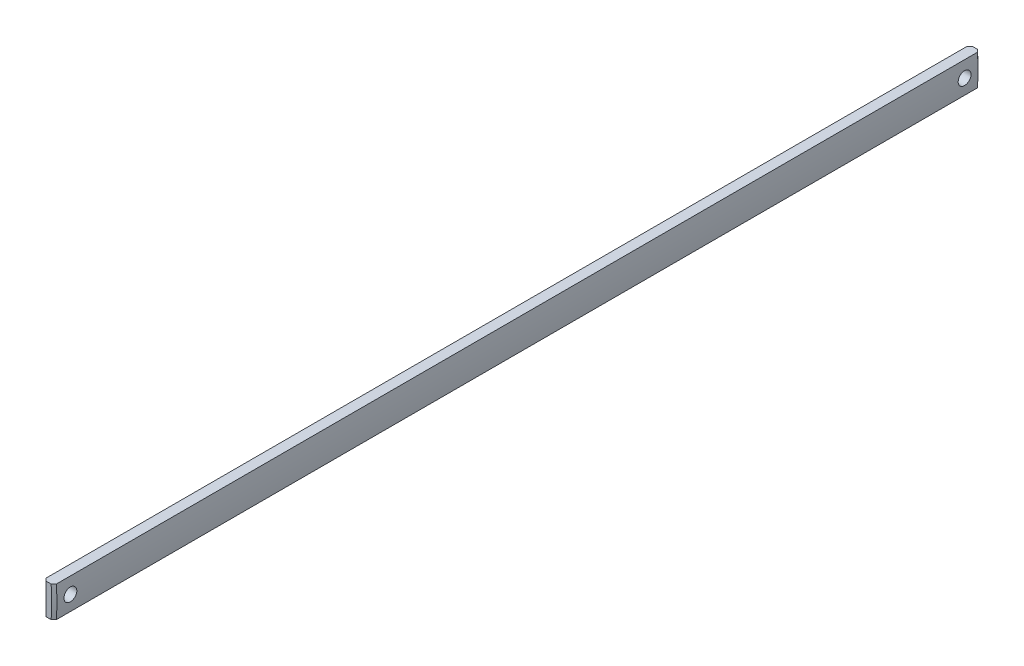
SolidWorks part; units mm, degrees
material "7075-T6, Piastra (SS)"
ref_plane "Piano frontale" through (0, 0, 0) normal (0, 0, 1) x (1, 0, 0)
ref_plane "Piano superiore" through (0, 0, 0) normal (0, 1, 0) x (1, 0, 0)
ref_plane "Piano destro" through (0, 0, 0) normal (1, 0, 0) x (0, 0, -1)
sketch "Schizzo1" plane through (0, 0, 0) normal (0, 0, 1) x (1, 0, 0)
  line L0 (68.753, 6) -> (68.753, -6)
  line L1 (68.753, -6) -> (72.753, -6)
  line L2 (68.753, 6) -> (72.753, 6)
  arc A0 (72.753, 6) -> (72.753, -6) centre (0, 0) cw
extrude "Estrusione-Estrusione1" add sketch "Schizzo1" along normal up to surface (360 mm away)
chamfer "Smusso1" distance 1 angle 45 4 edges at (68.753, 0, 360) (68.753, 0, 0) (73, 0, 360) (73, 0, 0)
sketch "Schizzo2" plane through (68.753, 0, 0) normal (-1, 0, 0) x (0, 0, 1)
  circle A0 centre (6.2292, 0) radius 2.5
extrude "Taglio-Estrusione1" cut sketch "Schizzo2" against normal through all separate body
ref_plane "Piano1" through (0, 0, 180) normal (0, 0, -1) x (-1, 0, 0)
mirror "Specchia1" about plane through (0, 0, 180) normal (0, 0, -1) of "Taglio-Estrusione1"
